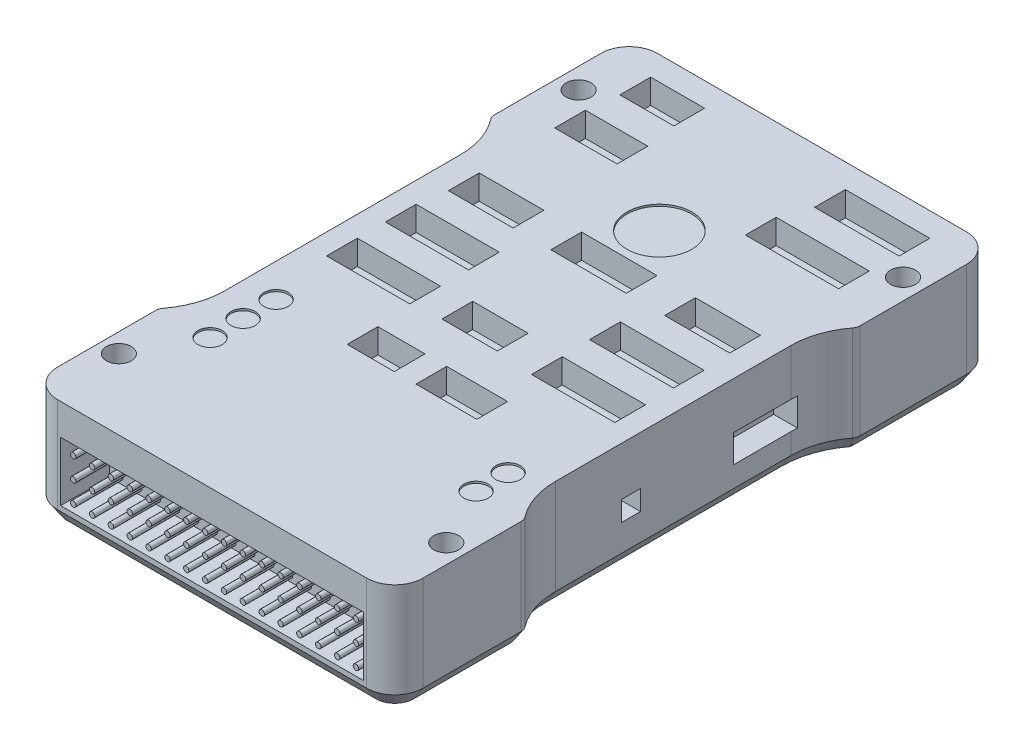
SolidWorks part; units mm, degrees
ref_plane "Front Plane" through (0, 0, 0) normal (0, 0, 1) x (1, 0, 0)
ref_plane "Top Plane" through (0, 0, 0) normal (0, 1, 0) x (1, 0, 0)
ref_plane "Right Plane" through (0, 0, 0) normal (1, 0, 0) x (0, 0, -1)
sketch "Sketch1" plane through (0, 0, 0) normal (0, 1, 0) x (1, 0, 0)
  line L0 (-22.2631, 21.0058) -> (-22.2631, -22.1234)
  line L1 (-24.6253, 40.4114) -> (24.6253, 40.4114)
  line L2 (-24.6253, 40.4114) -> (-24.6253, 22.2758)
  line L3 (-24.6253, -40.4114) -> (24.6253, -40.4114)
  line L4 (24.6253, 40.4114) -> (24.6253, 22.2758)
  line L5 (-24.6253, 40.4114) -> (24.6253, -40.4114) construction
  line L6 (-24.6253, -40.4114) -> (24.6253, 40.4114) construction
  line L7 (-24.6253, -23.3934) -> (-24.6253, -40.4114)
  line L8 (0, 40.4114) -> (0, -40.4114) construction
  line L9 (-23.3553, 21.0058) -> (-22.2631, 21.0058)
  line L10 (-23.3553, -22.1234) -> (-22.2631, -22.1234)
  line L11 (24.6253, -23.3934) -> (24.6253, -40.4114)
  line L12 (22.2631, 21.0058) -> (22.2631, -22.1234)
  line L13 (22.2631, 21.0058) -> (23.3553, 21.0058)
  line L14 (22.2631, -22.1234) -> (23.3553, -22.1234)
  arc A0 (-23.3553, -22.1234) -> (-24.6253, -23.3934) centre (-23.3553, -23.3934) ccw
  arc A1 (23.3553, -22.1234) -> (24.6253, -23.3934) centre (23.3553, -23.3934) cw
  arc A2 (23.3553, 21.0058) -> (24.6253, 22.2758) centre (23.3553, 22.2758) ccw
  arc A3 (-23.3553, 21.0058) -> (-24.6253, 22.2758) centre (-23.3553, 22.2758) cw
  point P0 (0, 0)
  point P18 (-24.6253, -22.1234)
  point P21 (24.6253, -22.1234)
  dimension "D4" = 1.27
  dimension "D1" = 49.2506
  dimension "D2" = 80.8228
  dimension "D3" = 44.5262
  dimension "D5" = 19.4056
  dimension "D6" = 18.288
extrude "Boss-Extrude2" add sketch "Sketch1" along normal blind 14.732
sketch "Sketch2" plane through (0, 0, 40.4114) normal (0, 0, 1) x (1, 0, 0)
  line L0 (-24.6253, 7.366) -> (24.6253, 7.366) construction
  line L1 (-24.6253, 14.732) -> (-24.6253, 0) construction
  line L2 (24.6253, 14.732) -> (24.6253, 0) construction
  line L3 (0, 14.732) -> (0, 0) construction
  line L4 (-24.6253, 14.732) -> (24.6253, 14.732) construction
  line L6 (-20.4216, 10.541) -> (20.4216, 10.541)
  line L7 (-20.4216, 10.541) -> (-20.4216, 2.5654)
  line L8 (-20.4216, 2.5654) -> (20.4216, 2.5654)
  line L9 (20.4216, 10.541) -> (20.4216, 2.5654)
  point P11 (0, 7.366)
  dimension "D1" = 4.191
  dimension "D2" = 40.8432
  dimension "D3" = 7.9756
  dimension "D4" = 4.2037
extrude "Cut-Extrude1" cut sketch "Sketch2" against normal blind 6.5786
sketch "Sketch3" plane through (0, 0, 33.8328) normal (0, 0, 1) x (1, 0, 0)
  line L0 (19.1516, 10.541) -> (19.1516, 2.5654) construction
  line L1 (20.4216, 10.541) -> (-20.4216, 10.541) construction
  line L2 (-20.4216, 2.5654) -> (20.4216, 2.5654) construction
  line L3 (20.4216, 2.5654) -> (20.4216, 10.541) construction
  line L4 (-20.4216, 9.017) -> (20.4216, 9.017) construction
  line L5 (-20.4216, 10.541) -> (-20.4216, 2.5654) construction
  line L7 (20.4216, 10.541) -> (-20.4216, 10.541) construction
  circle A0 centre (19.1516, 9.017) radius 0.3683
  dimension "D1" = 1.27
  dimension "D2" = 1.524
extrude "Boss-Extrude4" add sketch "Sketch3" along normal blind 6.35
pattern_linear "LPattern1" count 16 spacing 2.54 along (-1, 0, 0) count 3 spacing 2.8194 along (0, -1, 0) of "Boss-Extrude4"
sketch "Sketch4" plane through (0, 14.732, 0) normal (0, 1, 0) x (1, 0, 0)
  line L0 (-24.6253, -31.0134) -> (24.6253, -31.0134) construction
  line L1 (-24.6253, -23.3934) -> (-24.6253, -40.4114) construction
  line L2 (24.6253, -40.4114) -> (24.6253, -23.3934) construction
  line L3 (-24.6253, -40.4114) -> (24.6253, -40.4114) construction
  line L4 (22.0599, -21.4184) -> (22.0599, -40.4114) construction
  circle A0 centre (22.0599, -30.9149) radius 1.6764
  dimension "D1" = 9.398
  dimension "D2" = 2.5654
extrude "Cut-Extrude2" cut sketch "Sketch4" against normal blind 9.398
sketch "Sketch5" plane through (0, 14.732, 0) normal (0, 1, 0) x (1, 0, 0)
  line L0 (22.0599, -30.9149) -> (-24.6253, -30.9149) construction
  line L1 (-24.6253, -23.3934) -> (-24.6253, -40.4114) construction
  line L2 (-22.0599, -40.4114) -> (-22.0599, -18.735) construction
  line L3 (-24.6253, -40.4114) -> (24.6253, -40.4114) construction
  circle A0 centre (-22.0599, -30.9149) radius 1.6764
  dimension "D1" = 2.5654
extrude "Cut-Extrude3" cut sketch "Sketch5" against normal blind 6.35
sketch "Sketch6" plane through (0, 14.732, 0) normal (0, 1, 0) x (1, 0, 0)
  line L0 (-24.6253, 30.8356) -> (24.6253, 30.8356) construction
  line L1 (-24.6253, 40.4114) -> (-24.6253, 22.2758) construction
  line L2 (24.6253, 22.2758) -> (24.6253, 40.4114) construction
  line L3 (24.6253, 40.4114) -> (-24.6253, 40.4114) construction
  line L4 (21.8567, 40.4114) -> (21.8567, 21.1491) construction
  line L5 (-21.8567, 40.4114) -> (-21.8567, 21.6682) construction
  circle A0 centre (-21.8567, 30.8356) radius 1.6764
  circle A1 centre (21.8567, 30.8356) radius 1.6764
  dimension "D1" = 9.5758
  dimension "D2" = 2.7686
  dimension "D3" = 2.7686
extrude "Cut-Extrude4" cut sketch "Sketch6" against normal blind 6.35
sketch "Sketch7" plane through (0, 14.732, 0) normal (0, 1, 0) x (1, 0, 0)
  line L0 (-24.6253, -22.8854) -> (24.6253, -22.8854) construction
  line L1 (-24.6253, -23.3934) -> (-24.6253, -40.4114) construction
  line L2 (24.6253, -40.4114) -> (24.6253, -23.3934) construction
  line L3 (-24.6253, -40.4114) -> (24.6253, -40.4114) construction
  line L4 (18.0467, 40.4114) -> (18.0467, -22.8854) construction
  line L5 (24.6253, 40.4114) -> (-24.6253, 40.4114) construction
  line L6 (-22.2631, -18.5674) -> (22.2631, -18.5674) construction
  line L7 (-22.2631, 21.0058) -> (-22.2631, -22.1234) construction
  line L8 (22.2631, -22.1234) -> (22.2631, 21.0058) construction
  circle A0 centre (18.0467, -22.8854) radius 1.6383
  circle A1 centre (18.0467, -18.5674) radius 1.6383
  dimension "D3" = 4.318
  dimension "D1" = 17.526
  dimension "D2" = 6.5786
extrude "Cut-Extrude5" cut sketch "Sketch7" against normal blind 0.254
sketch "Sketch8" plane through (0, 14.732, 0) normal (0, 1, 0) x (1, 0, 0)
  line L0 (-17.7927, -40.4114) -> (-17.7927, 0.204) construction
  line L1 (-24.6253, -40.4114) -> (24.6253, -40.4114) construction
  line L3 (-24.6253, -23.3934) -> (-24.6253, -40.4114) construction
  line L4 (-24.6253, -22.8854) -> (-11.8136, -22.8854) construction
  circle A0 centre (-17.7927, -22.8854) radius 1.6383
  dimension "D1" = 6.8326
  dimension "D2" = 17.526
extrude "Cut-Extrude6" cut sketch "Sketch8" against normal blind 0.254
pattern_linear "LPattern3" count 3 spacing 4.445 along (0, 0, -1) of "Cut-Extrude6"
sketch "Sketch9" plane through (0, 14.732, 0) normal (0, 1, 0) x (1, 0, 0)
  line L0 (0, 40.4114) -> (0, -40.4114) construction
  line L1 (24.6253, 40.4114) -> (-24.6253, 40.4114) construction
  line L2 (-24.6253, -40.4114) -> (24.6253, -40.4114) construction
  line L3 (-22.2631, -0.5588) -> (22.2631, -0.5588) construction
  line L4 (-22.2631, 21.0058) -> (-22.2631, -22.1234) construction
  line L5 (22.2631, -22.1234) -> (22.2631, 21.0058) construction
  line L6 (-24.6253, 40.4114) -> (-24.6253, 22.2758) construction
  line L7 (-18.5039, 37.1856) -> (-11.2395, 37.1856)
  line L8 (-18.5039, 37.1856) -> (-18.5039, 33.0454)
  line L9 (-18.5039, 33.0454) -> (-11.2395, 33.0454)
  line L10 (-11.2395, 37.1856) -> (-11.2395, 33.0454)
  line L11 (24.6253, 22.2758) -> (24.6253, 40.4114) construction
  line L12 (7.7343, 37.1856) -> (19.1135, 37.1856)
  line L13 (7.7343, 37.1856) -> (7.7343, 33.0454)
  line L14 (7.7343, 33.0454) -> (19.1135, 33.0454)
  line L15 (19.1135, 37.1856) -> (19.1135, 33.0454)
  line L17 (-19.0373, 28.9306) -> (-10.6299, 28.9306)
  line L18 (-19.0373, 28.9306) -> (-19.0373, 24.7904)
  line L19 (-19.0373, 24.7904) -> (-10.6299, 24.7904)
  line L20 (-10.6299, 28.9306) -> (-10.6299, 24.7904)
  line L21 (6.3119, 29.2862) -> (18.8595, 29.2862)
  line L22 (6.3119, 29.2862) -> (6.3119, 25.146)
  line L23 (6.3119, 25.146) -> (18.8595, 25.146)
  line L24 (18.8595, 29.2862) -> (18.8595, 25.146)
  line L25 (-5.08, 14.4526) -> (5.08, 14.4526)
  line L26 (-5.08, 14.4526) -> (-5.08, 10.3124)
  line L27 (-5.08, 10.3124) -> (5.08, 10.3124)
  line L28 (5.08, 14.4526) -> (5.08, 10.3124)
  line L29 (-5.08, 14.4526) -> (5.08, 10.3124) construction
  line L30 (-5.08, 10.3124) -> (5.08, 14.4526) construction
  line L31 (10.2616, 14.4526) -> (19.0246, 14.4526)
  line L32 (10.2616, 14.4526) -> (10.2616, 10.3124)
  line L33 (10.2616, 10.3124) -> (19.0246, 10.3124)
  line L34 (19.0246, 14.4526) -> (19.0246, 10.3124)
  line L35 (-18.8722, 14.4526) -> (-10.16, 14.4526)
  line L36 (-18.8722, 14.4526) -> (-18.8722, 10.3124)
  line L37 (-18.8722, 10.3124) -> (-10.16, 10.3124)
  line L38 (-10.16, 14.4526) -> (-10.16, 10.3124)
  point P32 (0, 12.3825)
  dimension "D1" = 3.2258
  dimension "D2" = 6.1214
  dimension "D3" = 7.2644
  dimension "D4" = 4.1402
  dimension "D5" = 4.1402
  dimension "D6" = 3.2258
  dimension "D7" = 11.3792
  dimension "D8" = 5.5118
  dimension "D9" = 4.1148
  dimension "D10" = 4.1402
  dimension "D11" = 5.588
  dimension "D12" = 8.4074
  dimension "D13" = 4.1402
  dimension "D14" = 3.7592
  dimension "D15" = 12.5476
  dimension "D16" = 5.7658
  dimension "D17" = 25.9588
  dimension "D18" = 10.16
  dimension "D19" = 4.1402
  dimension "D20" = 5.1816
  dimension "D21" = 8.763
  dimension "D22" = 4.1402
  dimension "D23" = 5.08
  dimension "D24" = 8.7122
  dimension "D25" = 4.1402
  dimension "D26" = 25.9588
extrude "Cut-Extrude7" cut sketch "Sketch9" against normal blind 3.302
sketch "Sketch10" plane through (0, 14.732, 0) normal (0, 1, 0) x (1, 0, 0)
  line L0 (10.2616, 10.3124) -> (19.0246, 10.3124) construction
  line L1 (8.0137, 6.5786) -> (19.3167, 6.5786)
  line L2 (8.0137, 6.5786) -> (8.0137, 2.4384)
  line L3 (8.0137, 2.4384) -> (19.3167, 2.4384)
  line L4 (19.3167, 6.5786) -> (19.3167, 2.4384)
  line L5 (22.2631, -22.1234) -> (22.2631, 21.0058) construction
  line L6 (-22.2631, 21.0058) -> (-22.2631, -22.1234) construction
  line L7 (-19.4691, 6.5532) -> (-8.2677, 6.5532)
  line L8 (-19.4691, 6.5532) -> (-19.4691, 2.413)
  line L9 (-19.4691, 2.413) -> (-8.2677, 2.413)
  line L10 (-8.2677, 6.5532) -> (-8.2677, 2.413)
  line L11 (-18.8722, 10.3124) -> (-10.16, 10.3124) construction
  line L12 (-5.08, 10.3124) -> (5.08, 10.3124) construction
  line L13 (-19.4691, -5.5118) -> (-8.2677, -5.5118)
  line L14 (-19.4691, -5.5118) -> (-19.4691, -1.3716)
  line L15 (-19.4691, -1.3716) -> (-8.2677, -1.3716)
  line L16 (-8.2677, -5.5118) -> (-8.2677, -1.3716)
  line L17 (3.1369, -0.9652) -> (-4.3307, -0.9652)
  line L18 (3.1369, -0.9652) -> (3.1369, -5.1054)
  line L19 (3.1369, -5.1054) -> (-4.3307, -5.1054)
  line L20 (-4.3307, -0.9652) -> (-4.3307, -5.1054)
  line L22 (8.1661, -1.397) -> (19.3929, -1.397)
  line L23 (8.1661, -1.397) -> (8.1661, -5.5372)
  line L24 (8.1661, -5.5372) -> (19.3929, -5.5372)
  line L25 (19.3929, -1.397) -> (19.3929, -5.5372)
  dimension "D1" = 4.1402
  dimension "D2" = 3.7338
  dimension "D3" = 11.303
  dimension "D4" = 2.9464
  dimension "D5" = 2.794
  dimension "D6" = 4.1402
  dimension "D7" = 3.7592
  dimension "D8" = 11.2014
  dimension "D9" = 4.1402
  dimension "D10" = 3.7846
  dimension "D11" = 2.794
  dimension "D12" = 11.2014
  dimension "D13" = 3.937
  dimension "D14" = 7.4676
  dimension "D15" = 4.1402
  dimension "D16" = 11.2776
  dimension "D17" = 4.1402
  dimension "D18" = 2.8702
  dimension "D19" = 11.2268
  dimension "D20" = 3.8354
extrude "Cut-Extrude8" cut sketch "Sketch10" against normal blind 3.302
sketch "Sketch11" plane through (0, 14.732, 0) normal (0, 1, 0) x (1, 0, 0)
  line L0 (22.2631, -22.1234) -> (22.2631, 21.0058) construction
  line L1 (1.5113, -10.3124) -> (9.7155, -10.3124)
  line L2 (1.5113, -10.3124) -> (1.5113, -14.4526)
  line L3 (1.5113, -14.4526) -> (9.7155, -14.4526)
  line L4 (9.7155, -10.3124) -> (9.7155, -14.4526)
  line L5 (-4.3307, -5.1054) -> (3.1369, -5.1054) construction
  line L7 (-7.7597, -10.3124) -> (-1.4097, -10.3124)
  line L8 (-7.7597, -10.3124) -> (-7.7597, -14.4526)
  line L9 (-7.7597, -14.4526) -> (-1.4097, -14.4526)
  line L10 (-1.4097, -10.3124) -> (-1.4097, -14.4526)
  dimension "D1" = 12.5476
  dimension "D2" = 4.1402
  dimension "D3" = 8.2042
  dimension "D4" = 5.207
  dimension "D5" = 4.1402
  dimension "D6" = 2.921
  dimension "D7" = 6.35
  dimension "D8" = 5.207
extrude "Cut-Extrude9" cut sketch "Sketch11" against normal blind 3.302
sketch "Sketch12" plane through (0, 14.732, 0) normal (0, 1, 0) x (1, 0, 0)
  line L0 (0, 40.4114) -> (0, 10.3124) construction
  line L1 (24.6253, 40.4114) -> (-24.6253, 40.4114) construction
  line L2 (-5.08, 10.3124) -> (5.08, 10.3124) construction
  line L3 (5.08, 14.4526) -> (-5.08, 14.4526) construction
  circle A0 centre (0, 19.8628) radius 4.3688
  dimension "D1" = 5.4102
extrude "Cut-Extrude10" cut sketch "Sketch12" against normal blind 0.254
sketch "Sketch14" plane through (0, 0, -40.4114) normal (0, 0, -1) x (-1, 0, 0)
  line L0 (-24.6253, 14.732) -> (24.6253, 14.732) construction
  line L2 (-6.0325, 11.9126) -> (6.0325, 11.9126)
  line L3 (-6.0325, 11.9126) -> (-6.0325, 7.5692)
  line L4 (-6.0325, 7.5692) -> (6.0325, 7.5692)
  line L5 (0, 14.732) -> (0, 0) construction
  line L6 (6.0325, 11.9126) -> (6.0325, 7.5692)
  line L7 (-6.0325, 11.9126) -> (6.0325, 7.5692) construction
  line L8 (-6.0325, 7.5692) -> (6.0325, 11.9126) construction
  point P0 (0, 9.7409)
  dimension "D1" = 2.8194
  dimension "D2" = 12.065
  dimension "D3" = 4.3434
extrude "Cut-Extrude11" cut sketch "Sketch14" against normal blind 6.604
sketch "Sketch15" plane through (22.2631, 0, 0) normal (1, 0, 0) x (0, 0, -1)
  line L0 (-22.1234, 14.732) -> (21.0058, 14.732) construction
  line L1 (7.5946, 8.4328) -> (16.1798, 8.4328)
  line L2 (7.5946, 8.4328) -> (7.5946, 4.6736)
  line L3 (7.5946, 4.6736) -> (16.1798, 4.6736)
  line L4 (16.1798, 8.4328) -> (16.1798, 4.6736)
  line L5 (40.4114, 14.732) -> (40.4114, 0) construction
  dimension "D1" = 6.2992
  dimension "D2" = 3.7592
  dimension "D3" = 8.5852
  dimension "D4" = 24.2316
extrude "Cut-Extrude13" cut sketch "Sketch15" against normal blind 3.175
sketch "Sketch16" plane through (22.2631, 0, 0) normal (1, 0, 0) x (0, 0, -1)
  line L0 (7.5946, 8.4328) -> (7.5946, 4.6736) construction
  line L1 (-7.493, 8.1788) -> (-4.953, 8.1788)
  line L2 (-7.493, 8.1788) -> (-7.493, 5.4864)
  line L3 (-7.493, 5.4864) -> (-4.953, 5.4864)
  line L4 (-4.953, 8.1788) -> (-4.953, 5.4864)
  line L5 (-22.1234, 14.732) -> (21.0058, 14.732) construction
  dimension "D1" = 12.5476
  dimension "D2" = 6.5532
  dimension "D3" = 2.6924
  dimension "D4" = 2.54
extrude "Cut-Extrude14" cut sketch "Sketch16" against normal blind 2.54
sketch "Sketch18" plane through (-22.2631, 0, 0) normal (-1, 0, 0) x (0, 0, 1)
  line L0 (-21.0058, 14.732) -> (22.1234, 14.732) construction
  line L1 (4.2926, 8.9916) -> (6.858, 8.9916)
  line L2 (4.2926, 8.9916) -> (4.2926, 6.2992)
  line L3 (4.2926, 6.2992) -> (6.858, 6.2992)
  line L4 (6.858, 8.9916) -> (6.858, 6.2992)
  line L5 (40.4114, 14.732) -> (40.4114, 0) construction
  dimension "D1" = 5.7404
  dimension "D2" = 33.5534
  dimension "D3" = 2.5654
  dimension "D4" = 2.6924
extrude "Cut-Extrude15" cut sketch "Sketch18" against normal blind 2.54
fillet "Fillet2" radius 10.16 4 edges at (22.2631, 7.366, 22.1234) (-22.2631, 7.366, 22.1234) (-22.2631, 7.366, -21.0058) (22.2631, 7.366, -21.0058)
fillet "Fillet3" radius 3.81 4 edges at (-24.6253, 7.366, -40.4114) (24.6253, 7.366, -40.4114) (-24.6253, 7.366, 40.4114) (24.6253, 7.366, 40.4114)
sketch "Sketch20" plane through (0, 0, 0) normal (0, -1, 0) x (-1, 0, 0)
  text T0 "Bond, Mitch\r\nJuly 2017\r\nRevision 1" font "Century Gothic" height in points 8
extrude "Boss-Extrude5" add sketch "Sketch20" along normal blind 0.254
sketch "Sketch21" plane through (22.2631, 0, 0) normal (1, 0, 0) x (0, 0, -1)
  line L0 (-4.2926, 6.2992) -> (-4.2926, 2.4707) construction
sketch "Sketch22" plane through (0, 14.732, 0) normal (0, 1, 0) x (1, 0, 0)
  line L0 (20.1803, 30.8356) -> (20.1803, 40.4114) construction
  line L1 (20.8153, 40.4114) -> (-20.8153, 40.4114) construction
  circle A0 centre (21.8567, 30.8356) radius 1.6764 construction
  circle A1 centre (-17.7927, -13.9954) radius 1.6383 construction
sketch "Sketch23" plane through (0, 14.732, 0) normal (0, 1, 0) x (1, 0, 0)
  line L0 (-22.0599, -29.2385) -> (22.0599, -29.2385) construction
  circle A0 centre (-22.0599, -30.9149) radius 1.6764 construction
  circle A1 centre (22.0599, -30.9149) radius 1.6764 construction
sketch "Sketch24" plane through (0, 14.732, 0) normal (0, 1, 0) x (1, 0, 0)
  line L0 (-17.7927, -12.3571) -> (22.2631, -12.3571) construction
  line L1 (22.2631, -16.435) -> (22.2631, 15.3174) construction
  circle A0 centre (-17.7927, -13.9954) radius 1.6383 construction
sketch "Sketch25" plane through (0, 14.732, 0) normal (0, 1, 0) x (1, 0, 0)
  line L0 (19.0246, 14.4526) -> (22.2631, 14.4526) construction
  line L1 (22.2631, -16.435) -> (22.2631, 15.3174) construction
  line L2 (19.3929, -5.5372) -> (22.2631, -5.5372) construction
sketch "Sketch26" plane through (0, 14.732, 0) normal (0, 1, 0) x (1, 0, 0)
  line L0 (-22.2631, -0.5588) -> (22.2631, -0.5588) construction
  line L1 (-22.2631, 15.3174) -> (-22.2631, -16.435) construction
  line L2 (22.2631, -16.435) -> (22.2631, 15.3174) construction
sketch "Sketch27" plane through (0, 14.732, 0) normal (0, 1, 0) x (1, 0, 0)
  line L0 (19.0246, 10.3124) -> (22.2631, 10.3124) construction
  line L1 (22.2631, -16.435) -> (22.2631, 15.3174) construction
sketch "Sketch28" plane through (0, 14.732, 0) normal (0, 1, 0) x (1, 0, 0)
  line L0 (19.0881, 7.5946) -> (34.2661, 7.5946) construction
chamfer "Chamfer1" distance 1.27 angle 56 20 edges at (24.5579, 0, 22.9852) (22.8023, 0, 19.7009) (24.6253, 0, 29.9974) (23.5094, 0, 39.2955) (0, 0, 40.4114) (-23.5094, 0, 39.2955) (-24.6253, 0, 29.9974) (-24.5579, 0, 22.9852) (-22.8023, 0, 19.7009) (-22.2631, 0, 0.5588) (-22.8023, 0, -18.5833) (-24.5579, 0, -21.8676) (-24.6253, 0, -29.4386) (-23.5094, 0, -39.2955) (0, 0, -40.4114) (23.5094, 0, -39.2955) (24.6253, 0, -29.4386) (24.5579, 0, -21.8676) (22.8023, 0, -18.5833) (22.2631, 0, 0.5588) first distance on face at (-6.2998, 0, 4.9322)
